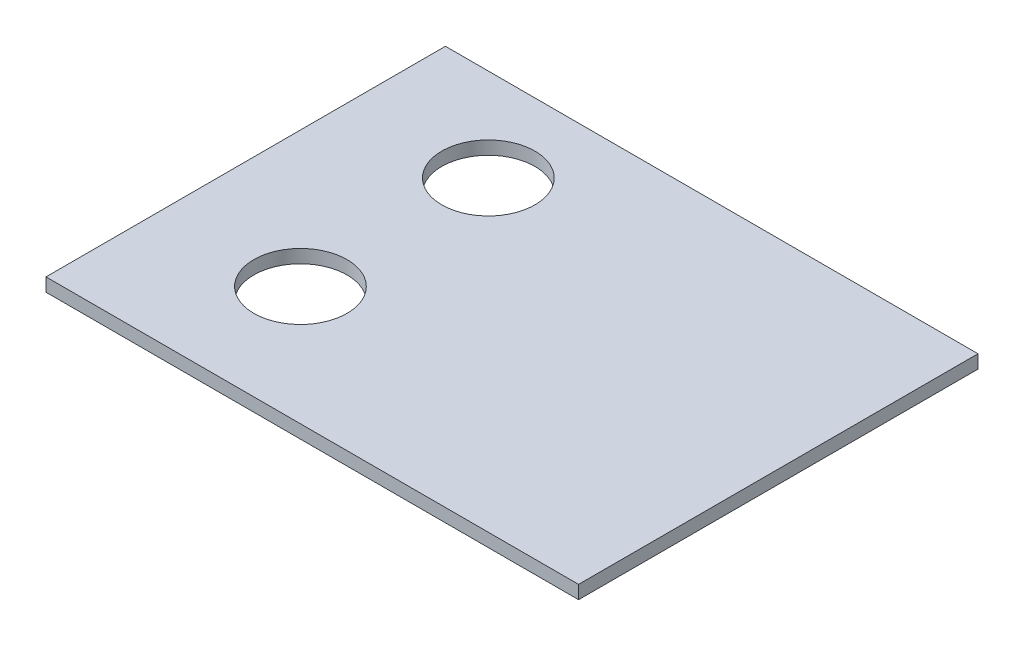
SolidWorks part; units mm, degrees
ref_plane "Alzado" through (0, 0, 0) normal (0, 0, 1) x (1, 0, 0)
ref_plane "Planta" through (0, 0, 0) normal (0, 1, 0) x (1, 0, 0)
ref_plane "Vista lateral" through (0, 0, 0) normal (1, 0, 0) x (0, 0, -1)
sketch "Croquis1" plane through (0, 0, 0) normal (0, 1, 0) x (1, 0, 0)
  line L1 (-20, 15) -> (20, 15)
  line L2 (-20, 15) -> (-20, -15)
  line L3 (-20, -15) -> (20, -15)
  line L4 (20, 15) -> (20, -15)
  line L5 (-20, 15) -> (20, -15) construction
  line L6 (-20, -15) -> (20, 15) construction
  point P0 (0, 0)
  dimension "D1" = 30
  dimension "D2" = 40
extrude "Saliente-Extruir1" add sketch "Croquis1" along normal blind 1
sketch "Croquis2" plane through (0, 1, 0) normal (0, 1, 0) x (1, 0, 0)
  circle A0 centre (-9.8216, 8.0461) radius 3.5
  circle A1 centre (-9.8216, -6.0683) radius 3.5
  dimension "D1" = 7
extrude "Cortar-Extruir1" cut sketch "Croquis2" against normal blind 10
